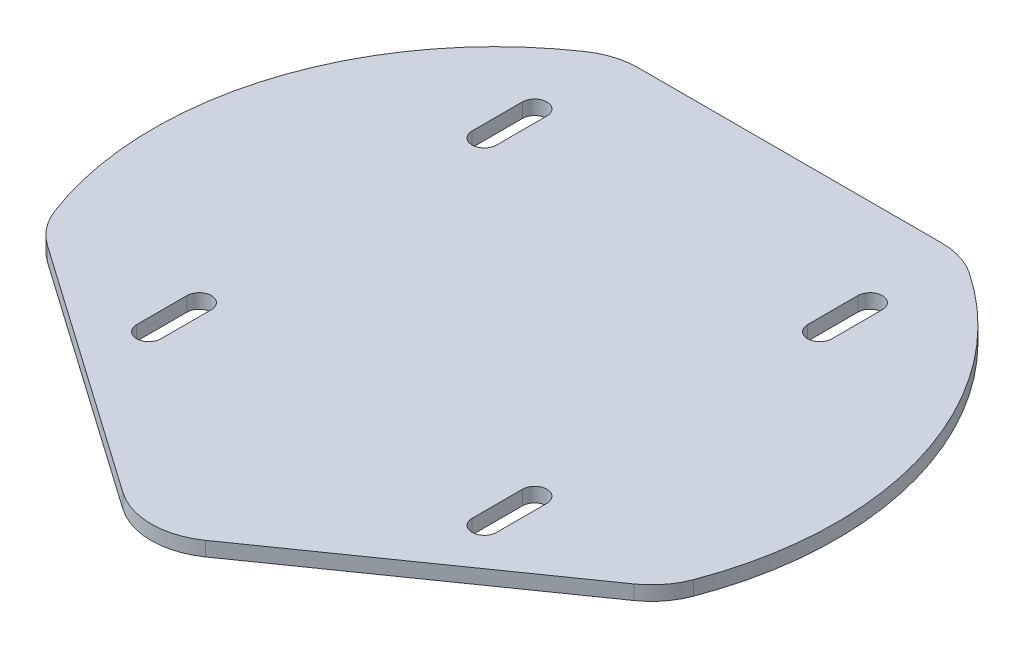
SolidWorks part; units mm, degrees
ref_plane "Plan de face" through (0, 0, 0) normal (0, 0, 1) x (1, 0, 0)
ref_plane "Plan de dessus" through (0, 0, 0) normal (0, 1, 0) x (1, 0, 0)
ref_plane "Plan de droite" through (0, 0, 0) normal (1, 0, 0) x (0, 0, -1)
sketch "Sketch1" plane through (0, 0, 0) normal (0, 1, 0) x (1, 0, 0)
  line L0 (0, 0) -> (0, 41) construction
  line L1 (0, 0) -> (-23.5166, -33.5852) construction
  line L2 (0, 0) -> (23.5166, -33.5852) construction
  line L3 (-43.1635, -19.8284) -> (0, -50.0518)
  line L4 (0, -50.0518) -> (43.1635, -19.8284)
  line L5 (-23.9844, 41) -> (23.9844, 41)
  arc A0 (-23.9844, 41) -> (-43.1635, -19.8284) centre (0, 0) ccw
  arc A1 (43.1635, -19.8284) -> (23.9844, 41) centre (0, 0) ccw
  point P1 (-46.255, -10.7723)
  point P8 (0, 0)
  point P12 (0, 0)
  point P13 (0, 0)
  dimension "D1" = 95
  dimension "D2" = 35
  dimension "D3" = 41
extrude "Boss-Extrude1" add sketch "Sketch1" along normal blind 2 contours L4 A0 L5 L3 region at (0, 0, -0.8358)
sketch "Esquisse1" plane through (0, 2, 0) normal (0, 1, 0) x (1, 0, 0)
  line L0 (0, 0) -> (-23.3345, 23.3345) construction
  line L1 (0, 0) -> (0, 41) construction
  line L2 (-23.9844, 41) -> (23.9844, 41) construction
  line L3 (-23.3345, 28.8345) -> (-23.3345, 21.8345) construction
  line L4 (-21.6345, 28.8345) -> (-21.6345, 21.8345)
  line L5 (-25.0345, 28.8345) -> (-25.0345, 21.8345)
  line L6 (0, 0) -> (23.3345, 23.3345) construction
  line L7 (0, 0) -> (23.3345, -23.3345) construction
  line L8 (0, 0) -> (-23.3345, -23.3345) construction
  line L9 (23.3345, 21.8345) -> (23.3345, 28.8345) construction
  line L10 (21.6345, 21.8345) -> (21.6345, 28.8345)
  line L11 (25.0345, 21.8345) -> (25.0345, 28.8345)
  line L12 (23.3345, -24.8345) -> (23.3345, -17.8345) construction
  line L13 (21.6345, -24.8345) -> (21.6345, -17.8345)
  line L14 (25.0345, -24.8345) -> (25.0345, -17.8345)
  line L15 (-23.3345, -24.8345) -> (-23.3345, -17.8345) construction
  line L16 (-25.0345, -24.8345) -> (-25.0345, -17.8345)
  line L17 (-21.6345, -24.8345) -> (-21.6345, -17.8345)
  arc A0 (-21.6345, 28.8345) -> (-25.0345, 28.8345) centre (-23.3345, 28.8345) ccw
  arc A1 (-25.0345, 21.8345) -> (-21.6345, 21.8345) centre (-23.3345, 21.8345) ccw
  arc A2 (21.6345, 21.8345) -> (25.0345, 21.8345) centre (23.3345, 21.8345) ccw
  arc A3 (25.0345, 28.8345) -> (21.6345, 28.8345) centre (23.3345, 28.8345) ccw
  arc A4 (21.6345, -24.8345) -> (25.0345, -24.8345) centre (23.3345, -24.8345) ccw
  arc A5 (25.0345, -17.8345) -> (21.6345, -17.8345) centre (23.3345, -17.8345) ccw
  arc A6 (-25.0345, -24.8345) -> (-21.6345, -24.8345) centre (-23.3345, -24.8345) ccw
  arc A7 (-21.6345, -17.8345) -> (-25.0345, -17.8345) centre (-23.3345, -17.8345) ccw
  point P8 (-23.3345, 25.3345)
  point P18 (23.3345, 25.3345)
  point P25 (23.3345, -21.3345)
  point P30 (-23.3345, -21.3345)
  point P37 (23.3345, 20.5604)
  point P38 (-23.3345, -26.2639)
  point P39 (0, 0)
  point P40 (0, 0)
  point P41 (23.3345, -27.4115)
  dimension "D5" = 1.7
  dimension "D1" = 1.5
  dimension "D2" = 5.5
  dimension "D3" = 45
  dimension "D4" = 33
  dimension "D6" = 45
  dimension "D7" = 1.5
extrude "Enlèv. mat.-Extru.1" cut sketch "Esquisse1" against normal up to next
fillet "Congé1" radius 10 5 edges at (43.1635, 1, 19.8284) (23.9844, 1, -41) (-23.9844, 1, -41) (-43.1635, 1, 19.8284) (0, 1, 50.0518)
